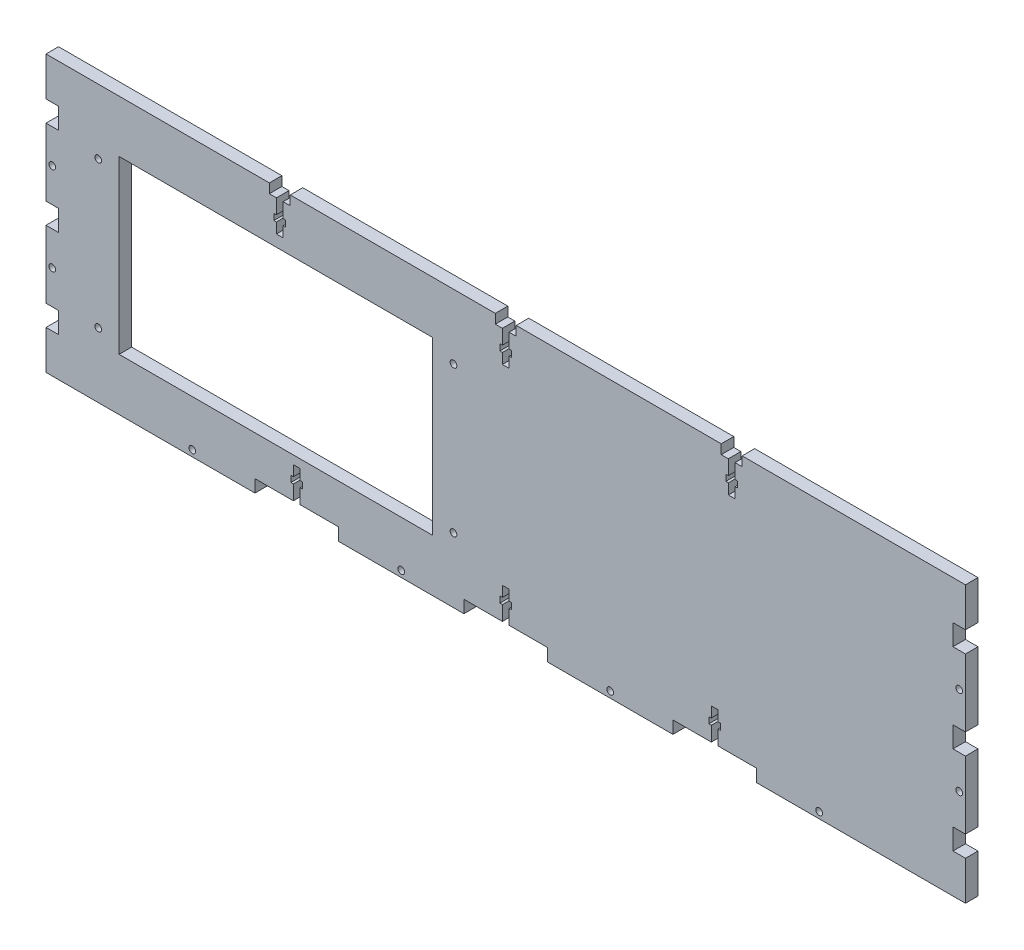
SolidWorks part; units mm, degrees
ref_plane "Front Plane" through (0, 0, 0) normal (0, 0, 1) x (1, 0, 0)
ref_plane "Top Plane" through (0, 0, 0) normal (0, 1, 0) x (1, 0, 0)
ref_plane "Right Plane" through (0, 0, 0) normal (1, 0, 0) x (0, 0, -1)
sketch "Sketch1" plane through (0, 0, 0) normal (0, 0, 1) x (1, 0, 0)
  line L1 (-220, -66) -> (220, -66)
  line L2 (-220, -66) -> (-220, 66)
  line L3 (-220, 66) -> (220, 66)
  line L4 (220, -66) -> (220, 66)
  line L5 (-220, -66) -> (220, 66) construction
  line L6 (-220, 66) -> (220, -66) construction
  point P0 (0, 0)
  dimension "D1" = 440
  dimension "D2" = 132
extrude "Boss-Extrude1" add sketch "Sketch1" along normal blind 6
sketch "Sketch2" plane through (0, 0, 0) normal (0, 0, -1) x (-1, 0, 0)
  line L0 (220, 47.3321) -> (220, 37.3321) construction
  line L1 (220, 37.3321) -> (214, 37.3321) construction
  line L2 (214, 37.3321) -> (214, 47.3321) construction
  line L3 (214, 47.3321) -> (220, 47.3321) construction
  line L12 (220, -37.3321) -> (220, -47.3321) construction
  line L13 (220, -47.3321) -> (214, -47.3321) construction
  line L14 (214, -47.3321) -> (214, -37.3321) construction
  line L15 (214, -37.3321) -> (220, -37.3321) construction
  line L16 (220, 47.3321) -> (220, 37.3321)
  line L17 (220, 37.3321) -> (214, 37.3321)
  line L18 (214, 37.3321) -> (214, 47.3321)
  line L19 (214, 47.3321) -> (220, 47.3321)
  line L20 (220, -37.3321) -> (220, -47.3321)
  line L21 (220, -47.3321) -> (214, -47.3321)
  line L22 (214, -47.3321) -> (214, -37.3321)
  line L23 (214, -37.3321) -> (220, -37.3321)
  line L24 (-214, -37.3321) -> (-214, -47.3321) construction
  line L25 (-214, -47.3321) -> (-220, -47.3321) construction
  line L26 (-220, -47.3321) -> (-220, -37.3321) construction
  line L27 (-220, -37.3321) -> (-214, -37.3321) construction
  line L28 (-214, 47.3321) -> (-214, 37.3321) construction
  line L29 (-214, 37.3321) -> (-220, 37.3321) construction
  line L30 (-220, 37.3321) -> (-220, 47.3321) construction
  line L31 (-220, 47.3321) -> (-214, 47.3321) construction
  line L32 (-214, -37.3321) -> (-214, -47.3321)
  line L33 (-214, -47.3321) -> (-220, -47.3321)
  line L34 (-220, -47.3321) -> (-220, -37.3321)
  line L35 (-220, -37.3321) -> (-214, -37.3321)
  line L36 (-214, 47.3321) -> (-214, 37.3321)
  line L37 (-214, 37.3321) -> (-220, 37.3321)
  line L38 (-220, 37.3321) -> (-220, 47.3321)
  line L39 (-220, 47.3321) -> (-214, 47.3321)
  line L44 (220, -5) -> (220, 5)
  line L45 (214, -5) -> (220, -5)
  line L46 (214, 5) -> (214, -5)
  line L47 (220, 5) -> (214, 5)
  line L48 (220, -5) -> (220, 5)
  line L49 (214, -5) -> (220, -5)
  line L50 (214, 5) -> (214, -5)
  line L51 (220, 5) -> (214, 5)
  line L52 (-214, -5) -> (-214, 5)
  line L53 (-220, -5) -> (-214, -5)
  line L54 (-220, 5) -> (-220, -5)
  line L55 (-214, 5) -> (-220, 5)
  line L56 (-214, -5) -> (-214, 5)
  line L57 (-220, -5) -> (-214, -5)
  line L58 (-220, 5) -> (-220, -5)
  line L59 (-214, 5) -> (-220, 5)
  circle A0 centre (217, 21.1661) radius 1.6 construction
  circle A1 centre (217, -21.1661) radius 1.6 construction
  circle A2 centre (-217, 21.1661) radius 1.6 construction
  circle A3 centre (-217, -21.1661) radius 1.6 construction
  circle A4 centre (217, 21.1661) radius 1.6
  circle A5 centre (217, -21.1661) radius 1.6
  circle A6 centre (-217, 21.1661) radius 1.6
  circle A7 centre (-217, -21.1661) radius 1.6
  dimension "D2" = 0
  dimension "D3" = 0
extrude "Cut-Extrude1" cut sketch "Sketch2" against normal up to next
sketch "Sketch3" plane through (0, 0, 0) normal (0, 0, -1) x (-1, 0, 0)
  circle A0 centre (-150, -63) radius 1.6 construction
  circle A1 centre (-50, -63) radius 1.6 construction
  circle A2 centre (50, -63) radius 1.6 construction
  circle A3 centre (150, -63) radius 1.6 construction
  circle A4 centre (-150, -63) radius 1.6
  circle A5 centre (-50, -63) radius 1.6
  circle A6 centre (50, -63) radius 1.6
  circle A7 centre (150, -63) radius 1.6
extrude "Cut-Extrude2" cut sketch "Sketch3" against normal up to next
sketch "Sketch4" plane through (0, 0, 0) normal (0, 0, -1) x (-1, 0, 0)
  line L0 (80, -66) -> (120, -66) construction
  line L1 (120, -66) -> (120, -60) construction
  line L2 (120, -60) -> (80, -60) construction
  line L3 (80, -60) -> (80, -66) construction
  line L4 (-20, -66) -> (20, -66) construction
  line L5 (20, -66) -> (20, -60) construction
  line L6 (20, -60) -> (-20, -60) construction
  line L7 (-20, -60) -> (-20, -66) construction
  line L8 (-120, -66) -> (-80, -66) construction
  line L9 (-80, -66) -> (-80, -60) construction
  line L10 (-80, -60) -> (-120, -60) construction
  line L11 (-120, -60) -> (-120, -66) construction
  line L12 (80, -66) -> (120, -66)
  line L13 (120, -66) -> (120, -60)
  line L14 (120, -60) -> (80, -60)
  line L15 (80, -60) -> (80, -66)
  line L16 (-20, -66) -> (20, -66)
  line L17 (20, -66) -> (20, -60)
  line L18 (20, -60) -> (-20, -60)
  line L19 (-20, -60) -> (-20, -66)
  line L20 (-120, -66) -> (-80, -66)
  line L21 (-80, -66) -> (-80, -60)
  line L22 (-80, -60) -> (-120, -60)
  line L23 (-120, -60) -> (-120, -66)
extrude "Cut-Extrude3" cut sketch "Sketch4" against normal up to next
sketch "Sketch5" plane through (0, 66, 0) normal (0, 1, 0) x (1, 0, 0)
  line L0 (220, 0) -> (-220, 0) construction
  line L1 (-113.125, -6) -> (-103.125, -6)
  line L2 (-113.125, -6) -> (-113.125, 0)
  line L3 (-113.125, 0) -> (-103.125, 0)
  line L4 (-103.125, -6) -> (-103.125, 0)
  line L5 (-113.125, -6) -> (-103.125, 0) construction
  line L6 (-113.125, 0) -> (-103.125, -6) construction
  line L7 (-103.125, -6) -> (-103.125, 0) construction
  line L8 (5, -6) -> (5, 0) construction
  line L9 (-5, -6) -> (5, -6)
  line L10 (-5, -6) -> (-5, 0)
  line L11 (-5, 0) -> (5, 0)
  line L12 (5, -6) -> (5, 0)
  line L13 (-5, -6) -> (5, 0) construction
  line L14 (-5, 0) -> (5, -6) construction
  line L15 (113.125, -6) -> (113.125, 0) construction
  line L16 (103.125, -6) -> (113.125, -6)
  line L17 (103.125, -6) -> (103.125, 0)
  line L18 (103.125, 0) -> (113.125, 0)
  line L19 (113.125, -6) -> (113.125, 0)
  line L20 (103.125, -6) -> (113.125, 0) construction
  line L21 (103.125, 0) -> (113.125, -6) construction
  point P0 (-108.125, -3)
  point P10 (0, -3)
  point P18 (108.125, -3)
extrude "Cut-Extrude4" cut sketch "Sketch5" against normal blind 4.5
sketch "Sketch6" plane through (0, 0, 0) normal (0, 0, -1) x (-1, 0, 0)
  line L0 (-108.125, 61.5) -> (-108.125, 46.5) construction
  line L1 (-113.125, 61.5) -> (-103.125, 61.5) construction
  line L2 (-109.725, 61.5) -> (-109.725, 54.5)
  line L3 (-106.525, 61.5) -> (-106.525, 54.5)
  line L4 (-109.725, 61.5) -> (-106.525, 61.5)
  line L5 (-109.725, 46.5) -> (-106.525, 46.5)
  line L6 (-106.525, 51.5) -> (-105.325, 51.5)
  line L7 (-110.925, 54.5) -> (-109.725, 54.5)
  line L8 (-110.925, 54.5) -> (-110.925, 51.5)
  line L9 (-110.925, 51.5) -> (-109.725, 51.5)
  line L10 (-105.325, 54.5) -> (-105.325, 51.5)
  line L11 (-110.925, 54.5) -> (-105.325, 51.5) construction
  line L12 (-110.925, 51.5) -> (-105.325, 54.5) construction
  line L13 (-106.525, 51.5) -> (-106.525, 46.5)
  line L14 (-106.525, 61.5) -> (-106.525, 46.5) construction
  line L15 (-109.725, 51.5) -> (-109.725, 46.5)
  line L16 (-109.725, 61.5) -> (-109.725, 46.5) construction
  line L17 (-106.525, 54.5) -> (-105.325, 54.5)
  line L18 (-1.595, 61.5) -> (-1.595, 54.5)
  line L19 (1.605, 61.5) -> (1.605, 54.5)
  line L20 (-1.595, 61.5) -> (1.605, 61.5)
  line L21 (-1.595, 46.5) -> (1.605, 46.5)
  line L22 (1.605, 51.5) -> (2.805, 51.5)
  line L23 (-2.795, 54.5) -> (-1.595, 54.5)
  line L24 (-2.795, 54.5) -> (-2.795, 51.5)
  line L25 (-2.795, 51.5) -> (-1.595, 51.5)
  line L26 (2.805, 54.5) -> (2.805, 51.5)
  line L27 (1.605, 51.5) -> (1.605, 46.5)
  line L28 (-1.595, 51.5) -> (-1.595, 46.5)
  line L29 (1.605, 54.5) -> (2.805, 54.5)
  line L30 (0.005, 61.5) -> (0.005, 46.5) construction
  line L31 (-2.795, 54.5) -> (2.805, 51.5) construction
  line L32 (-2.795, 51.5) -> (2.805, 54.5) construction
  line L33 (106.535, 61.5) -> (106.535, 54.5)
  line L34 (109.735, 61.5) -> (109.735, 54.5)
  line L35 (106.535, 61.5) -> (109.735, 61.5)
  line L36 (106.535, 46.5) -> (109.735, 46.5)
  line L37 (109.735, 51.5) -> (110.935, 51.5)
  line L38 (105.335, 54.5) -> (106.535, 54.5)
  line L39 (105.335, 54.5) -> (105.335, 51.5)
  line L40 (105.335, 51.5) -> (106.535, 51.5)
  line L41 (110.935, 54.5) -> (110.935, 51.5)
  line L42 (109.735, 51.5) -> (109.735, 46.5)
  line L43 (106.535, 51.5) -> (106.535, 46.5)
  line L44 (109.735, 54.5) -> (110.935, 54.5)
  line L45 (108.135, 61.5) -> (108.135, 46.5) construction
  line L46 (105.335, 54.5) -> (110.935, 51.5) construction
  line L47 (105.335, 51.5) -> (110.935, 54.5) construction
  line L48 (-100, -60) -> (-100, -45) construction
  line L49 (-80, -60) -> (-120, -60) construction
  line L50 (-98.4, -60) -> (-98.4, -53)
  line L51 (-101.6, -60) -> (-101.6, -53)
  line L52 (-98.4, -60) -> (-101.6, -60)
  line L53 (-98.4, -45) -> (-101.6, -45)
  line L54 (-98.4, -53) -> (-97.2, -53)
  line L55 (-102.8, -50) -> (-101.6, -50)
  line L56 (-102.8, -50) -> (-102.8, -53)
  line L57 (-102.8, -53) -> (-101.6, -53)
  line L58 (-97.2, -50) -> (-97.2, -53)
  line L59 (-102.8, -50) -> (-97.2, -53) construction
  line L60 (-102.8, -53) -> (-97.2, -50) construction
  line L61 (-98.4, -50) -> (-98.4, -45)
  line L62 (-98.4, -60) -> (-98.4, -45) construction
  line L63 (-98.4, -50) -> (-97.2, -50)
  line L64 (-101.6, -50) -> (-101.6, -45)
  line L65 (-101.6, -60) -> (-101.6, -45) construction
  line L66 (1.6, -60) -> (1.6, -53)
  line L67 (1.6, -60) -> (-1.6, -60)
  line L68 (-1.6, -60) -> (-1.6, -53)
  line L69 (-2.8, -53) -> (-1.6, -53)
  line L70 (-2.8, -50) -> (-2.8, -53)
  line L71 (-2.8, -50) -> (-1.6, -50)
  line L72 (-1.6, -50) -> (-1.6, -45)
  line L73 (1.6, -45) -> (-1.6, -45)
  line L74 (1.6, -50) -> (1.6, -45)
  line L75 (1.6, -50) -> (2.8, -50)
  line L76 (2.8, -50) -> (2.8, -53)
  line L77 (1.6, -53) -> (2.8, -53)
  line L78 (101.6, -60) -> (101.6, -53)
  line L79 (101.6, -60) -> (98.4, -60)
  line L80 (98.4, -60) -> (98.4, -53)
  line L81 (97.2, -53) -> (98.4, -53)
  line L82 (97.2, -50) -> (97.2, -53)
  line L83 (97.2, -50) -> (98.4, -50)
  line L84 (98.4, -50) -> (98.4, -45)
  line L85 (101.6, -45) -> (98.4, -45)
  line L86 (101.6, -50) -> (101.6, -45)
  line L87 (101.6, -50) -> (102.8, -50)
  line L88 (102.8, -50) -> (102.8, -53)
  line L89 (101.6, -53) -> (102.8, -53)
  point P8 (-108.125, 53)
  point P25 (0.005, 53)
  point P40 (108.135, 53)
  point P55 (-100, -51.5)
  dimension "D1" = 15
  dimension "D4" = 5.6
  dimension "D5" = 3
  dimension "D6" = 7
  dimension "D8" = 15
  dimension "D11" = 7
  dimension "D12" = 3
  dimension "D13" = 5.6
  dimension "D2" = 1.6
  dimension "D3" = 1.6
  dimension "D9" = 1.6
  dimension "D10" = 1.6
  dimension "D7" = 3
  dimension "D14" = 3
extrude "Cut-Extrude5" cut sketch "Sketch6" against normal up to next
sketch "Sketch7" plane through (0, 0, 0) normal (0, 0, -1) x (-1, 0, 0)
  line L0 (0, 0) -> (220, 0) construction
  line L1 (220, 37.3321) -> (220, 5) construction
  line L2 (113.125, 66) -> (220, 66) construction
  line L3 (35, -41) -> (185, -41)
  line L4 (35, -41) -> (35, 41)
  line L5 (35, 41) -> (185, 41)
  line L6 (185, -41) -> (185, 41)
  line L7 (35, -41) -> (185, 41) construction
  line L8 (35, 41) -> (185, -41) construction
  line L9 (25, 35) -> (25, -35) construction
  line L10 (25, 35) -> (195, 35) construction
  line L11 (25, -35) -> (35, -35) construction
  line L12 (195, -35) -> (185, -35) construction
  circle A0 centre (25, 35) radius 1.6
  circle A1 centre (25, -35) radius 1.6
  circle A2 centre (195, 35) radius 1.6
  circle A3 centre (195, -35) radius 1.6
  point P3 (110, 0)
  point P4 (110, 0)
  point P21 (110, 35)
  point P22 (25, 0)
  dimension "D5" = 3.2
  dimension "D1" = 25
  dimension "D2" = 150
  dimension "D3" = 10
  dimension "D4" = 70
extrude "Cut-Extrude6" cut sketch "Sketch7" against normal through all
equation "\"m3_depth\"=15"
equation "\"D1@Sketch6\"=\"m3_depth\""
equation "\"m3_nut_width\"=5.6"
equation "\"D4@Sketch6\"=\"m3_nut_width\""
equation "\"m3_nut_thickness\"=3"
equation "\"D5@Sketch6\"=\"m3_nut_thickness\""
equation "\"m3_nut_depth\"=7"
equation "\"D6@Sketch6\"=\"m3_nut_depth\""
